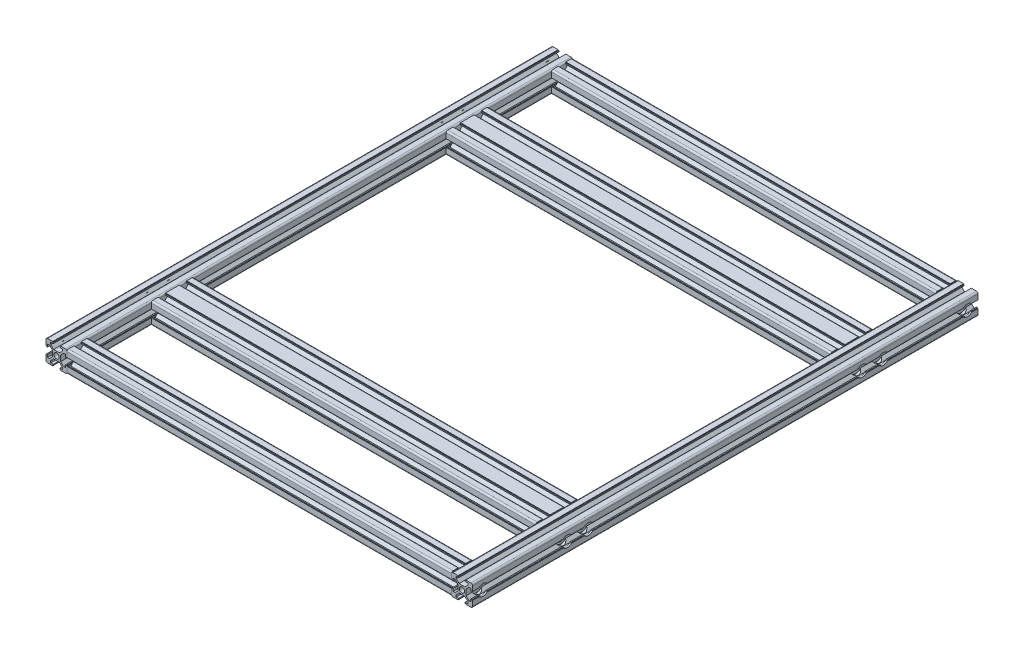
SolidWorks part; units mm, degrees
ref_plane "前视基准面" through (0, 0, 0) normal (0, 0, 1) x (1, 0, 0)
ref_plane "上视基准面" through (0, 0, 0) normal (0, 1, 0) x (1, 0, 0)
ref_plane "右视基准面" through (0, 0, 0) normal (1, 0, 0) x (0, 0, -1)
other "Configuration Table"
sketch "草图1" plane through (0, 0, 0) normal (0, 1, 0) x (1, 0, 0)
  line L0 (-192.5, 150) -> (-192.5, 230)
  line L1 (-192.5, 150) -> (192.5, 150)
  line L2 (-192.5, 150) -> (-192.5, -150)
  line L3 (-192.5, -150) -> (192.5, -150)
  line L4 (192.5, 150) -> (192.5, -150)
  line L5 (-192.5, 150) -> (192.5, -150) construction
  line L6 (-192.5, -150) -> (192.5, 150) construction
  line L7 (-192.5, 230) -> (192.5, 230)
  line L8 (192.5, 230) -> (192.5, 150)
  line L9 (-192.5, -150) -> (-192.5, -230)
  line L10 (-192.5, -230) -> (192.5, -230)
  line L11 (192.5, -230) -> (192.5, -150)
  point P0 (0, 0)
  dimension "D1" = 385
  dimension "D2" = 300
  dimension "D3" = 80
  dimension "D4" = 80
ref_plane "基准面1" through (-192.5, 0, -150) normal (0, 0, 1) x (1, 0, 0)
ref_plane "基准面2" through (-192.5, 0, 150) normal (1, 0, 0) x (0, 0, -1)
other "铝型材 20 X 20 X R1.5(1)"
ref_plane "基准面3" through (-192.5, 0, -230) normal (1, 0, 0) x (0, 0, -1)
sketch "Sketch1" plane through (-192.5, 0, -230) normal (1, 0, 0) x (0, 0, -1)
  line L0 (-3.6, 10) -> (-3.6, 9.5)
  line L1 (-3.6, 9.5) -> (-3.1, 9.5)
  line L2 (-3.1, 9.5) -> (-3.1, 8.5)
  line L3 (-3.1, 8.5) -> (-5.5, 8.5)
  line L4 (-8.5, -10) -> (-3.6, -10)
  line L5 (-10, -8.5) -> (-10, -3.6)
  line L6 (8.5, 10) -> (3.6, 10)
  line L7 (10, 8.5) -> (10, 3.6)
  line L8 (0, 14.8756) -> (0, 0) construction
  line L9 (0, 0) -> (14.1675, 0) construction
  line L10 (-5.5, 8.5) -> (-5.5, 6.65)
  line L11 (-5.5, 6.65) -> (-2.75, 3.9)
  line L12 (-2.75, 3.9) -> (2.75, 3.9)
  line L13 (5.5, 6.65) -> (2.75, 3.9)
  line L14 (5.5, 8.5) -> (5.5, 6.65)
  line L15 (3.1, 8.5) -> (5.5, 8.5)
  line L16 (3.1, 9.5) -> (3.1, 8.5)
  line L17 (3.6, 9.5) -> (3.1, 9.5)
  line L18 (3.6, 10) -> (3.6, 9.5)
  line L19 (-3.6, 10) -> (-8.5, 10)
  line L20 (10, 3.6) -> (9.5, 3.6)
  line L21 (9.5, 3.6) -> (9.5, 3.1)
  line L22 (9.5, 3.1) -> (8.5, 3.1)
  line L23 (8.5, 3.1) -> (8.5, 5.5)
  line L24 (8.5, 5.5) -> (6.65, 5.5)
  line L25 (6.65, 5.5) -> (3.9, 2.75)
  line L26 (3.9, 2.75) -> (3.9, -2.75)
  line L27 (6.65, -5.5) -> (3.9, -2.75)
  line L28 (8.5, -5.5) -> (6.65, -5.5)
  line L29 (8.5, -3.1) -> (8.5, -5.5)
  line L30 (9.5, -3.1) -> (8.5, -3.1)
  line L31 (9.5, -3.6) -> (9.5, -3.1)
  line L32 (10, -3.6) -> (9.5, -3.6)
  line L33 (3.6, -10) -> (3.6, -9.5)
  line L34 (3.6, -9.5) -> (3.1, -9.5)
  line L35 (3.1, -9.5) -> (3.1, -8.5)
  line L36 (3.1, -8.5) -> (5.5, -8.5)
  line L37 (5.5, -8.5) -> (5.5, -6.65)
  line L38 (5.5, -6.65) -> (2.75, -3.9)
  line L39 (2.75, -3.9) -> (-2.75, -3.9)
  line L40 (-5.5, -6.65) -> (-2.75, -3.9)
  line L41 (-5.5, -8.5) -> (-5.5, -6.65)
  line L42 (-3.1, -8.5) -> (-5.5, -8.5)
  line L43 (-3.1, -9.5) -> (-3.1, -8.5)
  line L44 (-3.6, -9.5) -> (-3.1, -9.5)
  line L45 (-3.6, -10) -> (-3.6, -9.5)
  line L46 (-10, -3.6) -> (-9.5, -3.6)
  line L47 (-9.5, -3.6) -> (-9.5, -3.1)
  line L48 (-9.5, -3.1) -> (-8.5, -3.1)
  line L49 (-8.5, -3.1) -> (-8.5, -5.5)
  line L50 (-8.5, -5.5) -> (-6.65, -5.5)
  line L51 (-6.65, -5.5) -> (-3.9, -2.75)
  line L52 (-3.9, -2.75) -> (-3.9, 2.75)
  line L53 (-6.65, 5.5) -> (-3.9, 2.75)
  line L54 (-8.5, 5.5) -> (-6.65, 5.5)
  line L55 (-8.5, 3.1) -> (-8.5, 5.5)
  line L56 (-9.5, 3.1) -> (-8.5, 3.1)
  line L57 (-9.5, 3.6) -> (-9.5, 3.1)
  line L58 (-10, 3.6) -> (-9.5, 3.6)
  line L59 (3.6, -10) -> (8.5, -10)
  line L60 (-10, 3.6) -> (-10, 8.5)
  line L61 (10, -3.6) -> (10, -8.5)
  circle A0 centre (0, 0) radius 2.5
  arc A1 (-10, 8.5) -> (-8.5, 10) centre (-8.5, 8.5) cw
  arc A2 (10, 8.5) -> (8.5, 10) centre (8.5, 8.5) ccw
  arc A3 (-8.5, -10) -> (-10, -8.5) centre (-8.5, -8.5) cw
  arc A4 (8.5, -10) -> (10, -8.5) centre (8.5, -8.5) ccw
  point P0 (-10, 0)
  point P1 (10, 0)
  point P2 (0, 10)
  point P3 (0, -10)
  point P4 (0, 0)
  point P5 (-10, -10)
  point P6 (10, -10)
  point P7 (10, 10)
  point P8 (-10, 10)
  point P13 (0, 0)
  point P36 (-10, 10)
  point P39 (10, 10)
  dimension "D1" = 11
  dimension "D2" = 20
  dimension "D3" = 6.2
  dimension "D4" = 7.2
  dimension "D5" = 6.1
  dimension "D6" = 5
  dimension "D7" = 1.5
  dimension "D8" = 45
  dimension "D9" = 0.5
  dimension "D10" = 1
  dimension "D11" = 5.5
other "铝型材 20 X 40 X R1.5(3)"
ref_plane "基准面8" through (-192.5, 0, 150) normal (1, 0, 0) x (0, 1, 0)
sketch "Sketch110" plane through (-192.5, 0, 150) normal (1, 0, 0) x (0, 1, 0)
  line L0 (-3.6, 10) -> (-3.6, 9.5)
  line L1 (-3.6, 9.5) -> (-3.1, 9.5)
  line L2 (-3.1, 9.5) -> (-3.1, 8.5)
  line L3 (-3.1, 8.5) -> (-5.5, 8.5)
  line L4 (8.85, -10) -> (2.75, -3.9)
  line L5 (-10, -16.4) -> (-10, -3.6)
  line L6 (8.5, 10) -> (3.6, 10)
  line L7 (10, 8.5) -> (10, 3.6)
  line L8 (0, 14.8756) -> (0, 0) construction
  line L9 (0, 0) -> (10, 0) construction
  line L10 (-5.5, 8.5) -> (-5.5, 6.65)
  line L11 (-5.5, 6.65) -> (-2.75, 3.9)
  line L12 (-2.75, 3.9) -> (2.75, 3.9)
  line L13 (5.5, 6.65) -> (2.75, 3.9)
  line L14 (5.5, 8.5) -> (5.5, 6.65)
  line L15 (3.1, 8.5) -> (5.5, 8.5)
  line L16 (3.1, 9.5) -> (3.1, 8.5)
  line L17 (3.6, 9.5) -> (3.1, 9.5)
  line L18 (3.6, 10) -> (3.6, 9.5)
  line L19 (-3.6, 10) -> (-8.5, 10)
  line L20 (10, 3.6) -> (9.5, 3.6)
  line L21 (9.5, 3.6) -> (9.5, 3.1)
  line L22 (9.5, 3.1) -> (8.5, 3.1)
  line L23 (8.5, 3.1) -> (8.5, 5.5)
  line L24 (8.5, 5.5) -> (6.65, 5.5)
  line L25 (6.65, 5.5) -> (3.9, 2.75)
  line L26 (3.9, 2.75) -> (3.9, -2.75)
  line L27 (6.65, -5.5) -> (3.9, -2.75)
  line L28 (8.5, -5.5) -> (6.65, -5.5)
  line L29 (8.5, -3.1) -> (8.5, -5.5)
  line L30 (9.5, -3.1) -> (8.5, -3.1)
  line L31 (9.5, -3.6) -> (9.5, -3.1)
  line L32 (10, -3.6) -> (9.5, -3.6)
  line L33 (8.85, -10) -> (2.75, -16.1)
  line L34 (-8.85, -10) -> (-2.75, -16.1)
  line L35 (-8.85, -10) -> (-2.75, -3.9)
  line L39 (2.75, -3.9) -> (-2.75, -3.9)
  line L46 (-10, -3.6) -> (-9.5, -3.6)
  line L47 (-9.5, -3.6) -> (-9.5, -3.1)
  line L48 (-9.5, -3.1) -> (-8.5, -3.1)
  line L49 (-8.5, -3.1) -> (-8.5, -5.5)
  line L50 (-8.5, -5.5) -> (-6.65, -5.5)
  line L51 (-6.65, -5.5) -> (-3.9, -2.75)
  line L52 (-3.9, -2.75) -> (-3.9, 2.75)
  line L53 (-6.65, 5.5) -> (-3.9, 2.75)
  line L54 (-8.5, 5.5) -> (-6.65, 5.5)
  line L55 (-8.5, 3.1) -> (-8.5, 5.5)
  line L56 (-9.5, 3.1) -> (-8.5, 3.1)
  line L57 (-9.5, 3.6) -> (-9.5, 3.1)
  line L58 (-10, 3.6) -> (-9.5, 3.6)
  line L60 (-10, 3.6) -> (-10, 8.5)
  line L61 (10, -3.6) -> (10, -16.4)
  line L66 (-8.5, -30) -> (-3.6, -30)
  line L67 (-10, -28.5) -> (-10, -23.6)
  line L72 (-2.75, -16.1) -> (2.75, -16.1)
  line L80 (10, -16.4) -> (9.5, -16.4)
  line L81 (9.5, -16.4) -> (9.5, -16.9)
  line L82 (9.5, -16.9) -> (8.5, -16.9)
  line L83 (8.5, -16.9) -> (8.5, -14.5)
  line L84 (8.5, -14.5) -> (6.65, -14.5)
  line L85 (6.65, -14.5) -> (3.9, -17.25)
  line L86 (3.9, -17.25) -> (3.9, -22.75)
  line L87 (6.65, -25.5) -> (3.9, -22.75)
  line L88 (8.5, -25.5) -> (6.65, -25.5)
  line L89 (8.5, -23.1) -> (8.5, -25.5)
  line L90 (9.5, -23.1) -> (8.5, -23.1)
  line L91 (9.5, -23.6) -> (9.5, -23.1)
  line L92 (10, -23.6) -> (9.5, -23.6)
  line L93 (3.6, -30) -> (3.6, -29.5)
  line L94 (3.6, -29.5) -> (3.1, -29.5)
  line L95 (3.1, -29.5) -> (3.1, -28.5)
  line L96 (3.1, -28.5) -> (5.5, -28.5)
  line L97 (5.5, -28.5) -> (5.5, -26.65)
  line L98 (5.5, -26.65) -> (2.75, -23.9)
  line L99 (2.75, -23.9) -> (-2.75, -23.9)
  line L100 (-5.5, -26.65) -> (-2.75, -23.9)
  line L101 (-5.5, -28.5) -> (-5.5, -26.65)
  line L102 (-3.1, -28.5) -> (-5.5, -28.5)
  line L103 (-3.1, -29.5) -> (-3.1, -28.5)
  line L104 (-3.6, -29.5) -> (-3.1, -29.5)
  line L105 (-3.6, -30) -> (-3.6, -29.5)
  line L106 (-10, -23.6) -> (-9.5, -23.6)
  line L107 (-9.5, -23.6) -> (-9.5, -23.1)
  line L108 (-9.5, -23.1) -> (-8.5, -23.1)
  line L109 (-8.5, -23.1) -> (-8.5, -25.5)
  line L110 (-8.5, -25.5) -> (-6.65, -25.5)
  line L111 (-6.65, -25.5) -> (-3.9, -22.75)
  line L112 (-3.9, -22.75) -> (-3.9, -17.25)
  line L113 (-6.65, -14.5) -> (-3.9, -17.25)
  line L114 (-8.5, -14.5) -> (-6.65, -14.5)
  line L115 (-8.5, -16.9) -> (-8.5, -14.5)
  line L116 (-9.5, -16.9) -> (-8.5, -16.9)
  line L117 (-9.5, -16.4) -> (-9.5, -16.9)
  line L118 (-10, -16.4) -> (-9.5, -16.4)
  line L119 (3.6, -30) -> (8.5, -30)
  line L121 (10, -23.6) -> (10, -28.5)
  line L122 (0, -20) -> (10, -20) construction
  line L125 (3.6, -10) -> (3.6, -9.5)
  line L127 (3.6, -9.5) -> (3.1, -9.5)
  line L129 (3.1, -9.5) -> (3.1, -8.5)
  line L131 (3.1, -8.5) -> (5.5, -8.5)
  line L133 (-3.1, -8.5) -> (-5.5, -8.5)
  line L135 (-3.1, -9.5) -> (-3.1, -8.5)
  line L137 (-3.6, -9.5) -> (-3.1, -9.5)
  line L139 (-3.6, -10) -> (-3.6, -9.5)
  line L141 (-3.6, -10) -> (-3.6, -10.5)
  line L142 (-3.6, -10.5) -> (-3.1, -10.5)
  line L143 (-3.1, -10.5) -> (-3.1, -11.5)
  line L144 (-3.1, -11.5) -> (-5.5, -11.5)
  line L145 (8.5, -10) -> (3.6, -10)
  line L146 (3.1, -11.5) -> (5.5, -11.5)
  line L147 (3.1, -10.5) -> (3.1, -11.5)
  line L148 (3.6, -10.5) -> (3.1, -10.5)
  line L149 (3.6, -10) -> (3.6, -10.5)
  line L150 (-3.6, -10) -> (-8.5, -10)
  line L151 (-10, -16.4) -> (-10, -11.5)
  line L152 (10, -11.5) -> (10, -16.4)
  line L154 (-5.5, -8.5) -> (-5.5, -6.65)
  line L156 (5.5, -8.5) -> (5.5, -6.65)
  line L157 (5.5, -11.5) -> (5.5, -13.35)
  line L158 (-5.5, -11.5) -> (-5.5, -13.35)
  line L160 (-12.2446, -13.3946) -> (-10, -11.15)
  line L161 (13.644, -5.206) -> (10, -8.85)
  line L163 (12.1963, -13.3463) -> (10, -11.15)
  line L164 (-11.1344, -7.7156) -> (-10, -8.85)
  circle A0 centre (0, 0) radius 2.5
  arc A1 (-10, 8.5) -> (-8.5, 10) centre (-8.5, 8.5) cw
  arc A2 (10, 8.5) -> (8.5, 10) centre (8.5, 8.5) ccw
  arc A3 (10, -28.5) -> (8.5, -30) centre (8.5, -28.5) cw
  arc A4 (-10, -28.5) -> (-8.5, -30) centre (-8.5, -28.5) ccw
  circle A5 centre (0, -20) radius 2.5
  arc A12 (-10, -11.5) -> (-8.5, -10) centre (-8.5, -11.5) cw
  arc A13 (10, -11.5) -> (8.5, -10) centre (8.5, -11.5) ccw
  point P0 (-10, 0)
  point P1 (10, 0)
  point P2 (0, 10)
  point P4 (0, 0)
  point P5 (0, -10)
  point P6 (-10, -10)
  point P7 (10, 10)
  point P8 (-10, 10)
  point P12 (-10, -10)
  point P13 (10, -10)
  point P15 (0, -10)
  point P16 (10, -10)
  point P36 (-10, 10)
  point P39 (10, 10)
  point P43 (-10, -20)
  point P44 (10, -20)
  point P62 (0, 0)
  point P88 (0, -30)
  point P89 (0, -20)
  point P90 (-10, -30)
  point P91 (10, -30)
  dimension "D1" = 11
  dimension "D2" = 20
  dimension "D3" = 6.2
  dimension "D4" = 7.2
  dimension "D5" = 6.1
  dimension "D6" = 5
  dimension "D7" = 1.5
  dimension "D8" = 45
  dimension "D14" = 20
  dimension "D15" = 1.5
  dimension "D9" = 0.5
  dimension "D10" = 1
  dimension "D11" = 5.5
  dimension "D12" = 10
  dimension "D13" = 40
  dimension "D16" = 45
  dimension "D17" = 45
  dimension "D18" = 45
  dimension "D19" = 6.2
other "铝型材 20 X 40 X R1.5(4)"
ref_plane "基准面9" through (-192.5, 0, -150) normal (1, 0, 0) x (0, -1, 0)
sketch "Sketch111" plane through (-192.5, 0, -150) normal (1, 0, 0) x (0, -1, 0)
  line L0 (-3.6, 10) -> (-3.6, 9.5)
  line L1 (-3.6, 9.5) -> (-3.1, 9.5)
  line L2 (-3.1, 9.5) -> (-3.1, 8.5)
  line L3 (-3.1, 8.5) -> (-5.5, 8.5)
  line L4 (8.85, -10) -> (2.75, -3.9)
  line L5 (-10, -16.4) -> (-10, -3.6)
  line L6 (8.5, 10) -> (3.6, 10)
  line L7 (10, 8.5) -> (10, 3.6)
  line L8 (0, 14.8756) -> (0, 0) construction
  line L9 (0, 0) -> (10, 0) construction
  line L10 (-5.5, 8.5) -> (-5.5, 6.65)
  line L11 (-5.5, 6.65) -> (-2.75, 3.9)
  line L12 (-2.75, 3.9) -> (2.75, 3.9)
  line L13 (5.5, 6.65) -> (2.75, 3.9)
  line L14 (5.5, 8.5) -> (5.5, 6.65)
  line L15 (3.1, 8.5) -> (5.5, 8.5)
  line L16 (3.1, 9.5) -> (3.1, 8.5)
  line L17 (3.6, 9.5) -> (3.1, 9.5)
  line L18 (3.6, 10) -> (3.6, 9.5)
  line L19 (-3.6, 10) -> (-8.5, 10)
  line L20 (10, 3.6) -> (9.5, 3.6)
  line L21 (9.5, 3.6) -> (9.5, 3.1)
  line L22 (9.5, 3.1) -> (8.5, 3.1)
  line L23 (8.5, 3.1) -> (8.5, 5.5)
  line L24 (8.5, 5.5) -> (6.65, 5.5)
  line L25 (6.65, 5.5) -> (3.9, 2.75)
  line L26 (3.9, 2.75) -> (3.9, -2.75)
  line L27 (6.65, -5.5) -> (3.9, -2.75)
  line L28 (8.5, -5.5) -> (6.65, -5.5)
  line L29 (8.5, -3.1) -> (8.5, -5.5)
  line L30 (9.5, -3.1) -> (8.5, -3.1)
  line L31 (9.5, -3.6) -> (9.5, -3.1)
  line L32 (10, -3.6) -> (9.5, -3.6)
  line L33 (8.85, -10) -> (2.75, -16.1)
  line L34 (-8.85, -10) -> (-2.75, -16.1)
  line L35 (-8.85, -10) -> (-2.75, -3.9)
  line L39 (2.75, -3.9) -> (-2.75, -3.9)
  line L46 (-10, -3.6) -> (-9.5, -3.6)
  line L47 (-9.5, -3.6) -> (-9.5, -3.1)
  line L48 (-9.5, -3.1) -> (-8.5, -3.1)
  line L49 (-8.5, -3.1) -> (-8.5, -5.5)
  line L50 (-8.5, -5.5) -> (-6.65, -5.5)
  line L51 (-6.65, -5.5) -> (-3.9, -2.75)
  line L52 (-3.9, -2.75) -> (-3.9, 2.75)
  line L53 (-6.65, 5.5) -> (-3.9, 2.75)
  line L54 (-8.5, 5.5) -> (-6.65, 5.5)
  line L55 (-8.5, 3.1) -> (-8.5, 5.5)
  line L56 (-9.5, 3.1) -> (-8.5, 3.1)
  line L57 (-9.5, 3.6) -> (-9.5, 3.1)
  line L58 (-10, 3.6) -> (-9.5, 3.6)
  line L60 (-10, 3.6) -> (-10, 8.5)
  line L61 (10, -3.6) -> (10, -16.4)
  line L66 (-8.5, -30) -> (-3.6, -30)
  line L67 (-10, -28.5) -> (-10, -23.6)
  line L72 (-2.75, -16.1) -> (2.75, -16.1)
  line L80 (10, -16.4) -> (9.5, -16.4)
  line L81 (9.5, -16.4) -> (9.5, -16.9)
  line L82 (9.5, -16.9) -> (8.5, -16.9)
  line L83 (8.5, -16.9) -> (8.5, -14.5)
  line L84 (8.5, -14.5) -> (6.65, -14.5)
  line L85 (6.65, -14.5) -> (3.9, -17.25)
  line L86 (3.9, -17.25) -> (3.9, -22.75)
  line L87 (6.65, -25.5) -> (3.9, -22.75)
  line L88 (8.5, -25.5) -> (6.65, -25.5)
  line L89 (8.5, -23.1) -> (8.5, -25.5)
  line L90 (9.5, -23.1) -> (8.5, -23.1)
  line L91 (9.5, -23.6) -> (9.5, -23.1)
  line L92 (10, -23.6) -> (9.5, -23.6)
  line L93 (3.6, -30) -> (3.6, -29.5)
  line L94 (3.6, -29.5) -> (3.1, -29.5)
  line L95 (3.1, -29.5) -> (3.1, -28.5)
  line L96 (3.1, -28.5) -> (5.5, -28.5)
  line L97 (5.5, -28.5) -> (5.5, -26.65)
  line L98 (5.5, -26.65) -> (2.75, -23.9)
  line L99 (2.75, -23.9) -> (-2.75, -23.9)
  line L100 (-5.5, -26.65) -> (-2.75, -23.9)
  line L101 (-5.5, -28.5) -> (-5.5, -26.65)
  line L102 (-3.1, -28.5) -> (-5.5, -28.5)
  line L103 (-3.1, -29.5) -> (-3.1, -28.5)
  line L104 (-3.6, -29.5) -> (-3.1, -29.5)
  line L105 (-3.6, -30) -> (-3.6, -29.5)
  line L106 (-10, -23.6) -> (-9.5, -23.6)
  line L107 (-9.5, -23.6) -> (-9.5, -23.1)
  line L108 (-9.5, -23.1) -> (-8.5, -23.1)
  line L109 (-8.5, -23.1) -> (-8.5, -25.5)
  line L110 (-8.5, -25.5) -> (-6.65, -25.5)
  line L111 (-6.65, -25.5) -> (-3.9, -22.75)
  line L112 (-3.9, -22.75) -> (-3.9, -17.25)
  line L113 (-6.65, -14.5) -> (-3.9, -17.25)
  line L114 (-8.5, -14.5) -> (-6.65, -14.5)
  line L115 (-8.5, -16.9) -> (-8.5, -14.5)
  line L116 (-9.5, -16.9) -> (-8.5, -16.9)
  line L117 (-9.5, -16.4) -> (-9.5, -16.9)
  line L118 (-10, -16.4) -> (-9.5, -16.4)
  line L119 (3.6, -30) -> (8.5, -30)
  line L121 (10, -23.6) -> (10, -28.5)
  line L122 (0, -20) -> (10, -20) construction
  line L125 (3.6, -10) -> (3.6, -9.5)
  line L127 (3.6, -9.5) -> (3.1, -9.5)
  line L129 (3.1, -9.5) -> (3.1, -8.5)
  line L131 (3.1, -8.5) -> (5.5, -8.5)
  line L133 (-3.1, -8.5) -> (-5.5, -8.5)
  line L135 (-3.1, -9.5) -> (-3.1, -8.5)
  line L137 (-3.6, -9.5) -> (-3.1, -9.5)
  line L139 (-3.6, -10) -> (-3.6, -9.5)
  line L141 (-3.6, -10) -> (-3.6, -10.5)
  line L142 (-3.6, -10.5) -> (-3.1, -10.5)
  line L143 (-3.1, -10.5) -> (-3.1, -11.5)
  line L144 (-3.1, -11.5) -> (-5.5, -11.5)
  line L145 (8.5, -10) -> (3.6, -10)
  line L146 (3.1, -11.5) -> (5.5, -11.5)
  line L147 (3.1, -10.5) -> (3.1, -11.5)
  line L148 (3.6, -10.5) -> (3.1, -10.5)
  line L149 (3.6, -10) -> (3.6, -10.5)
  line L150 (-3.6, -10) -> (-8.5, -10)
  line L151 (-10, -16.4) -> (-10, -11.5)
  line L152 (10, -11.5) -> (10, -16.4)
  line L154 (-5.5, -8.5) -> (-5.5, -6.65)
  line L156 (5.5, -8.5) -> (5.5, -6.65)
  line L157 (5.5, -11.5) -> (5.5, -13.35)
  line L158 (-5.5, -11.5) -> (-5.5, -13.35)
  line L160 (-12.2446, -13.3946) -> (-10, -11.15)
  line L161 (13.644, -5.206) -> (10, -8.85)
  line L163 (12.1963, -13.3463) -> (10, -11.15)
  line L164 (-11.1344, -7.7156) -> (-10, -8.85)
  circle A0 centre (0, 0) radius 2.5
  arc A1 (-10, 8.5) -> (-8.5, 10) centre (-8.5, 8.5) cw
  arc A2 (10, 8.5) -> (8.5, 10) centre (8.5, 8.5) ccw
  arc A3 (10, -28.5) -> (8.5, -30) centre (8.5, -28.5) cw
  arc A4 (-10, -28.5) -> (-8.5, -30) centre (-8.5, -28.5) ccw
  circle A5 centre (0, -20) radius 2.5
  arc A12 (-10, -11.5) -> (-8.5, -10) centre (-8.5, -11.5) cw
  arc A13 (10, -11.5) -> (8.5, -10) centre (8.5, -11.5) ccw
  point P0 (-10, 0)
  point P1 (10, 0)
  point P2 (0, 10)
  point P4 (0, 0)
  point P5 (0, -10)
  point P6 (-10, -10)
  point P7 (10, 10)
  point P8 (-10, 10)
  point P12 (-10, -10)
  point P13 (10, -10)
  point P15 (0, -10)
  point P16 (10, -10)
  point P36 (-10, 10)
  point P39 (10, 10)
  point P43 (-10, -20)
  point P44 (10, -20)
  point P62 (0, 0)
  point P88 (0, -30)
  point P89 (0, -20)
  point P90 (-10, -30)
  point P91 (10, -30)
  dimension "D1" = 11
  dimension "D2" = 20
  dimension "D3" = 6.2
  dimension "D4" = 7.2
  dimension "D5" = 6.1
  dimension "D6" = 5
  dimension "D7" = 1.5
  dimension "D8" = 45
  dimension "D14" = 20
  dimension "D15" = 1.5
  dimension "D9" = 0.5
  dimension "D10" = 1
  dimension "D11" = 5.5
  dimension "D12" = 10
  dimension "D13" = 40
  dimension "D16" = 45
  dimension "D17" = 45
  dimension "D18" = 45
  dimension "D19" = 6.2
other "铝型材 20 X 20 X R1.5(24)"
ref_plane "基准面10" through (-192.5, 0, 150) normal (0, 0, 1) x (1, 0, 0)
sketch "Sketch114" plane through (-192.5, 0, 150) normal (0, 0, 1) x (1, 0, 0)
  line L0 (-3.6, 10) -> (-3.6, 9.5)
  line L1 (-3.6, 9.5) -> (-3.1, 9.5)
  line L2 (-3.1, 9.5) -> (-3.1, 8.5)
  line L3 (-3.1, 8.5) -> (-5.5, 8.5)
  line L4 (-8.5, -10) -> (-3.6, -10)
  line L5 (-10, -8.5) -> (-10, -3.6)
  line L6 (8.5, 10) -> (3.6, 10)
  line L7 (10, 8.5) -> (10, 3.6)
  line L8 (0, 14.8756) -> (0, 0) construction
  line L9 (0, 0) -> (14.1675, 0) construction
  line L10 (-5.5, 8.5) -> (-5.5, 6.65)
  line L11 (-5.5, 6.65) -> (-2.75, 3.9)
  line L12 (-2.75, 3.9) -> (2.75, 3.9)
  line L13 (5.5, 6.65) -> (2.75, 3.9)
  line L14 (5.5, 8.5) -> (5.5, 6.65)
  line L15 (3.1, 8.5) -> (5.5, 8.5)
  line L16 (3.1, 9.5) -> (3.1, 8.5)
  line L17 (3.6, 9.5) -> (3.1, 9.5)
  line L18 (3.6, 10) -> (3.6, 9.5)
  line L19 (-3.6, 10) -> (-8.5, 10)
  line L20 (10, 3.6) -> (9.5, 3.6)
  line L21 (9.5, 3.6) -> (9.5, 3.1)
  line L22 (9.5, 3.1) -> (8.5, 3.1)
  line L23 (8.5, 3.1) -> (8.5, 5.5)
  line L24 (8.5, 5.5) -> (6.65, 5.5)
  line L25 (6.65, 5.5) -> (3.9, 2.75)
  line L26 (3.9, 2.75) -> (3.9, -2.75)
  line L27 (6.65, -5.5) -> (3.9, -2.75)
  line L28 (8.5, -5.5) -> (6.65, -5.5)
  line L29 (8.5, -3.1) -> (8.5, -5.5)
  line L30 (9.5, -3.1) -> (8.5, -3.1)
  line L31 (9.5, -3.6) -> (9.5, -3.1)
  line L32 (10, -3.6) -> (9.5, -3.6)
  line L33 (3.6, -10) -> (3.6, -9.5)
  line L34 (3.6, -9.5) -> (3.1, -9.5)
  line L35 (3.1, -9.5) -> (3.1, -8.5)
  line L36 (3.1, -8.5) -> (5.5, -8.5)
  line L37 (5.5, -8.5) -> (5.5, -6.65)
  line L38 (5.5, -6.65) -> (2.75, -3.9)
  line L39 (2.75, -3.9) -> (-2.75, -3.9)
  line L40 (-5.5, -6.65) -> (-2.75, -3.9)
  line L41 (-5.5, -8.5) -> (-5.5, -6.65)
  line L42 (-3.1, -8.5) -> (-5.5, -8.5)
  line L43 (-3.1, -9.5) -> (-3.1, -8.5)
  line L44 (-3.6, -9.5) -> (-3.1, -9.5)
  line L45 (-3.6, -10) -> (-3.6, -9.5)
  line L46 (-10, -3.6) -> (-9.5, -3.6)
  line L47 (-9.5, -3.6) -> (-9.5, -3.1)
  line L48 (-9.5, -3.1) -> (-8.5, -3.1)
  line L49 (-8.5, -3.1) -> (-8.5, -5.5)
  line L50 (-8.5, -5.5) -> (-6.65, -5.5)
  line L51 (-6.65, -5.5) -> (-3.9, -2.75)
  line L52 (-3.9, -2.75) -> (-3.9, 2.75)
  line L53 (-6.65, 5.5) -> (-3.9, 2.75)
  line L54 (-8.5, 5.5) -> (-6.65, 5.5)
  line L55 (-8.5, 3.1) -> (-8.5, 5.5)
  line L56 (-9.5, 3.1) -> (-8.5, 3.1)
  line L57 (-9.5, 3.6) -> (-9.5, 3.1)
  line L58 (-10, 3.6) -> (-9.5, 3.6)
  line L59 (3.6, -10) -> (8.5, -10)
  line L60 (-10, 3.6) -> (-10, 8.5)
  line L61 (10, -3.6) -> (10, -8.5)
  circle A0 centre (0, 0) radius 2.5
  arc A1 (-10, 8.5) -> (-8.5, 10) centre (-8.5, 8.5) cw
  arc A2 (10, 8.5) -> (8.5, 10) centre (8.5, 8.5) ccw
  arc A3 (-8.5, -10) -> (-10, -8.5) centre (-8.5, -8.5) cw
  arc A4 (8.5, -10) -> (10, -8.5) centre (8.5, -8.5) ccw
  point P0 (-10, 0)
  point P1 (10, 0)
  point P2 (0, 10)
  point P3 (0, -10)
  point P4 (0, 0)
  point P5 (-10, -10)
  point P6 (10, -10)
  point P7 (10, 10)
  point P8 (-10, 10)
  point P13 (0, 0)
  point P36 (-10, 10)
  point P39 (10, 10)
  dimension "D1" = 11
  dimension "D2" = 20
  dimension "D3" = 6.2
  dimension "D4" = 7.2
  dimension "D5" = 6.1
  dimension "D6" = 5
  dimension "D7" = 1.5
  dimension "D8" = 45
  dimension "D9" = 0.5
  dimension "D10" = 1
  dimension "D11" = 5.5
other "铝型材 20 X 20 X R1.5(25)"
ref_plane "基准面11" through (192.5, 0, 230) normal (0, 0, -1) x (-1, 0, 0)
sketch "Sketch115" plane through (192.5, 0, 230) normal (0, 0, -1) x (-1, 0, 0)
  line L0 (-3.6, 10) -> (-3.6, 9.5)
  line L1 (-3.6, 9.5) -> (-3.1, 9.5)
  line L2 (-3.1, 9.5) -> (-3.1, 8.5)
  line L3 (-3.1, 8.5) -> (-5.5, 8.5)
  line L4 (-8.5, -10) -> (-3.6, -10)
  line L5 (-10, -8.5) -> (-10, -3.6)
  line L6 (8.5, 10) -> (3.6, 10)
  line L7 (10, 8.5) -> (10, 3.6)
  line L8 (0, 14.8756) -> (0, 0) construction
  line L9 (0, 0) -> (14.1675, 0) construction
  line L10 (-5.5, 8.5) -> (-5.5, 6.65)
  line L11 (-5.5, 6.65) -> (-2.75, 3.9)
  line L12 (-2.75, 3.9) -> (2.75, 3.9)
  line L13 (5.5, 6.65) -> (2.75, 3.9)
  line L14 (5.5, 8.5) -> (5.5, 6.65)
  line L15 (3.1, 8.5) -> (5.5, 8.5)
  line L16 (3.1, 9.5) -> (3.1, 8.5)
  line L17 (3.6, 9.5) -> (3.1, 9.5)
  line L18 (3.6, 10) -> (3.6, 9.5)
  line L19 (-3.6, 10) -> (-8.5, 10)
  line L20 (10, 3.6) -> (9.5, 3.6)
  line L21 (9.5, 3.6) -> (9.5, 3.1)
  line L22 (9.5, 3.1) -> (8.5, 3.1)
  line L23 (8.5, 3.1) -> (8.5, 5.5)
  line L24 (8.5, 5.5) -> (6.65, 5.5)
  line L25 (6.65, 5.5) -> (3.9, 2.75)
  line L26 (3.9, 2.75) -> (3.9, -2.75)
  line L27 (6.65, -5.5) -> (3.9, -2.75)
  line L28 (8.5, -5.5) -> (6.65, -5.5)
  line L29 (8.5, -3.1) -> (8.5, -5.5)
  line L30 (9.5, -3.1) -> (8.5, -3.1)
  line L31 (9.5, -3.6) -> (9.5, -3.1)
  line L32 (10, -3.6) -> (9.5, -3.6)
  line L33 (3.6, -10) -> (3.6, -9.5)
  line L34 (3.6, -9.5) -> (3.1, -9.5)
  line L35 (3.1, -9.5) -> (3.1, -8.5)
  line L36 (3.1, -8.5) -> (5.5, -8.5)
  line L37 (5.5, -8.5) -> (5.5, -6.65)
  line L38 (5.5, -6.65) -> (2.75, -3.9)
  line L39 (2.75, -3.9) -> (-2.75, -3.9)
  line L40 (-5.5, -6.65) -> (-2.75, -3.9)
  line L41 (-5.5, -8.5) -> (-5.5, -6.65)
  line L42 (-3.1, -8.5) -> (-5.5, -8.5)
  line L43 (-3.1, -9.5) -> (-3.1, -8.5)
  line L44 (-3.6, -9.5) -> (-3.1, -9.5)
  line L45 (-3.6, -10) -> (-3.6, -9.5)
  line L46 (-10, -3.6) -> (-9.5, -3.6)
  line L47 (-9.5, -3.6) -> (-9.5, -3.1)
  line L48 (-9.5, -3.1) -> (-8.5, -3.1)
  line L49 (-8.5, -3.1) -> (-8.5, -5.5)
  line L50 (-8.5, -5.5) -> (-6.65, -5.5)
  line L51 (-6.65, -5.5) -> (-3.9, -2.75)
  line L52 (-3.9, -2.75) -> (-3.9, 2.75)
  line L53 (-6.65, 5.5) -> (-3.9, 2.75)
  line L54 (-8.5, 5.5) -> (-6.65, 5.5)
  line L55 (-8.5, 3.1) -> (-8.5, 5.5)
  line L56 (-9.5, 3.1) -> (-8.5, 3.1)
  line L57 (-9.5, 3.6) -> (-9.5, 3.1)
  line L58 (-10, 3.6) -> (-9.5, 3.6)
  line L59 (3.6, -10) -> (8.5, -10)
  line L60 (-10, 3.6) -> (-10, 8.5)
  line L61 (10, -3.6) -> (10, -8.5)
  circle A0 centre (0, 0) radius 2.5
  arc A1 (-10, 8.5) -> (-8.5, 10) centre (-8.5, 8.5) cw
  arc A2 (10, 8.5) -> (8.5, 10) centre (8.5, 8.5) ccw
  arc A3 (-8.5, -10) -> (-10, -8.5) centre (-8.5, -8.5) cw
  arc A4 (8.5, -10) -> (10, -8.5) centre (8.5, -8.5) ccw
  point P0 (-10, 0)
  point P1 (10, 0)
  point P2 (0, 10)
  point P3 (0, -10)
  point P4 (0, 0)
  point P5 (-10, -10)
  point P6 (10, -10)
  point P7 (10, 10)
  point P8 (-10, 10)
  point P13 (0, 0)
  point P36 (-10, 10)
  point P39 (10, 10)
  dimension "D1" = 11
  dimension "D2" = 20
  dimension "D3" = 6.2
  dimension "D4" = 7.2
  dimension "D5" = 6.1
  dimension "D6" = 5
  dimension "D7" = 1.5
  dimension "D8" = 45
  dimension "D9" = 0.5
  dimension "D10" = 1
  dimension "D11" = 5.5
other "剪裁/延伸3"
other "剪裁/延伸4"
other "剪裁/延伸5"
other "剪裁/延伸6"
combine bodies "组合1" operation type add bodies to combine 142 133 140
combine bodies "组合2" operation type add bodies to combine 141 130 139
sketch "草图16" plane through (-202.5, 0, 0) normal (-1, 0, 0) x (0, 0, 1)
  line L0 (121.5, 8.5) -> (140, -10) construction
  line L1 (140, -10) -> (158.5, 8.5) construction
  line L2 (153.9, 0) -> (126.1, 0) construction
  line L9 (-140, -8.85) -> (-133.9, -2.75)
  line L10 (-146.1, -2.75) -> (-140, -8.85)
  line L11 (-146.1, 2.75) -> (-146.1, -2.75)
  line L12 (-140, 8.85) -> (-146.1, 2.75)
  line L13 (-133.9, 2.75) -> (-140, 8.85)
  line L14 (-133.9, -2.75) -> (-133.9, 2.75)
  line L15 (-140, -8.85) -> (-133.9, -2.75)
  line L16 (-146.1, -2.75) -> (-140, -8.85)
  line L17 (-146.1, 2.75) -> (-146.1, -2.75)
  line L18 (-140, 8.85) -> (-146.1, 2.75)
  line L19 (-133.9, 2.75) -> (-140, 8.85)
  line L20 (-133.9, -2.75) -> (-133.9, 2.75)
  line L88 (160, -3.6) -> (159.5, -3.6)
  line L89 (159.5, -3.6) -> (159.5, -3.1)
  line L90 (159.5, -3.1) -> (158.5, -3.1)
  line L91 (158.5, -3.1) -> (158.5, -5.5)
  line L92 (158.5, -5.5) -> (156.65, -5.5)
  line L93 (156.65, -5.5) -> (153.9, -2.75)
  line L94 (153.9, -2.75) -> (153.9, 2.75)
  line L95 (153.9, 2.75) -> (156.65, 5.5)
  line L96 (156.65, 5.5) -> (158.5, 5.5)
  line L97 (158.5, 5.5) -> (158.5, 3.1)
  line L98 (158.5, 3.1) -> (159.5, 3.1)
  line L99 (159.5, 3.1) -> (159.5, 3.6)
  line L100 (159.5, 3.6) -> (160, 3.6)
  line L101 (160, 3.6) -> (160, 8.5)
  line L102 (158.5, 10) -> (153.6, 10)
  line L103 (153.6, 10) -> (153.6, 9.5)
  line L104 (153.6, 9.5) -> (153.1, 9.5)
  line L105 (153.1, 9.5) -> (153.1, 8.5)
  line L106 (153.1, 8.5) -> (155.5, 8.5)
  line L107 (155.5, 8.5) -> (155.5, 6.65)
  line L108 (155.5, 6.65) -> (152.75, 3.9)
  line L109 (152.75, 3.9) -> (147.25, 3.9)
  line L110 (147.25, 3.9) -> (144.5, 6.65)
  line L111 (144.5, 6.65) -> (144.5, 8.5)
  line L112 (144.5, 8.5) -> (146.9, 8.5)
  line L113 (146.9, 8.5) -> (146.9, 9.5)
  line L114 (146.9, 9.5) -> (146.4, 9.5)
  line L115 (146.4, 9.5) -> (146.4, 10)
  line L116 (146.4, 10) -> (133.6, 10)
  line L117 (133.6, 10) -> (133.6, 9.5)
  line L118 (133.6, 9.5) -> (133.1, 9.5)
  line L119 (133.1, 9.5) -> (133.1, 8.5)
  line L120 (133.1, 8.5) -> (135.5, 8.5)
  line L121 (135.5, 8.5) -> (135.5, 6.65)
  line L122 (135.5, 6.65) -> (132.75, 3.9)
  line L123 (132.75, 3.9) -> (127.25, 3.9)
  line L124 (127.25, 3.9) -> (124.5, 6.65)
  line L125 (124.5, 6.65) -> (124.5, 8.5)
  line L126 (124.5, 8.5) -> (126.9, 8.5)
  line L127 (126.9, 8.5) -> (126.9, 9.5)
  line L128 (126.9, 9.5) -> (126.4, 9.5)
  line L129 (126.4, 9.5) -> (126.4, 10)
  line L130 (126.4, 10) -> (121.5, 10)
  line L131 (120, 8.5) -> (120, 3.6)
  line L132 (120, 3.6) -> (120.5, 3.6)
  line L133 (120.5, 3.6) -> (120.5, 3.1)
  line L134 (120.5, 3.1) -> (121.5, 3.1)
  line L135 (121.5, 3.1) -> (121.5, 5.5)
  line L136 (121.5, 5.5) -> (123.35, 5.5)
  line L137 (123.35, 5.5) -> (126.1, 2.75)
  line L138 (126.1, 2.75) -> (126.1, -2.75)
  line L139 (126.1, -2.75) -> (123.35, -5.5)
  line L140 (123.35, -5.5) -> (121.5, -5.5)
  line L141 (121.5, -5.5) -> (121.5, -3.1)
  line L142 (121.5, -3.1) -> (120.5, -3.1)
  line L143 (120.5, -3.1) -> (120.5, -3.6)
  line L144 (120.5, -3.6) -> (120, -3.6)
  line L145 (120, -3.6) -> (120, -8.5)
  line L146 (121.5, -10) -> (126.4, -10)
  line L147 (126.4, -10) -> (126.4, -9.5)
  line L148 (126.4, -9.5) -> (126.9, -9.5)
  line L149 (126.9, -9.5) -> (126.9, -8.5)
  line L150 (126.9, -8.5) -> (124.5, -8.5)
  line L151 (124.5, -8.5) -> (124.5, -6.65)
  line L152 (124.5, -6.65) -> (127.25, -3.9)
  line L153 (127.25, -3.9) -> (132.75, -3.9)
  line L154 (132.75, -3.9) -> (135.5, -6.65)
  line L155 (135.5, -6.65) -> (135.5, -8.5)
  line L156 (135.5, -8.5) -> (133.1, -8.5)
  line L157 (133.1, -8.5) -> (133.1, -9.5)
  line L158 (133.1, -9.5) -> (133.6, -9.5)
  line L159 (133.6, -9.5) -> (133.6, -10)
  line L160 (133.6, -10) -> (146.4, -10)
  line L161 (146.4, -10) -> (146.4, -9.5)
  line L162 (146.4, -9.5) -> (146.9, -9.5)
  line L163 (146.9, -9.5) -> (146.9, -8.5)
  line L164 (146.9, -8.5) -> (144.5, -8.5)
  line L165 (144.5, -8.5) -> (144.5, -6.65)
  line L166 (144.5, -6.65) -> (147.25, -3.9)
  line L167 (147.25, -3.9) -> (152.75, -3.9)
  line L168 (152.75, -3.9) -> (155.5, -6.65)
  line L169 (155.5, -6.65) -> (155.5, -8.5)
  line L170 (155.5, -8.5) -> (153.1, -8.5)
  line L171 (153.1, -8.5) -> (153.1, -9.5)
  line L172 (153.1, -9.5) -> (153.6, -9.5)
  line L173 (153.6, -9.5) -> (153.6, -10)
  line L174 (153.6, -10) -> (158.5, -10)
  line L175 (160, -8.5) -> (160, -3.6)
  line L176 (160, -3.6) -> (159.5, -3.6)
  line L177 (159.5, -3.6) -> (159.5, -3.1)
  line L178 (159.5, -3.1) -> (158.5, -3.1)
  line L179 (158.5, -3.1) -> (158.5, -5.5)
  line L180 (158.5, -5.5) -> (156.65, -5.5)
  line L181 (156.65, -5.5) -> (153.9, -2.75)
  line L182 (153.9, -2.75) -> (153.9, 2.75)
  line L183 (153.9, 2.75) -> (156.65, 5.5)
  line L184 (156.65, 5.5) -> (158.5, 5.5)
  line L185 (158.5, 5.5) -> (158.5, 3.1)
  line L186 (158.5, 3.1) -> (159.5, 3.1)
  line L187 (159.5, 3.1) -> (159.5, 3.6)
  line L188 (159.5, 3.6) -> (160, 3.6)
  line L189 (160, 3.6) -> (160, 8.5)
  line L190 (158.5, 10) -> (153.6, 10)
  line L191 (153.6, 10) -> (153.6, 9.5)
  line L192 (153.6, 9.5) -> (153.1, 9.5)
  line L193 (153.1, 9.5) -> (153.1, 8.5)
  line L194 (153.1, 8.5) -> (155.5, 8.5)
  line L195 (155.5, 8.5) -> (155.5, 6.65)
  line L196 (155.5, 6.65) -> (152.75, 3.9)
  line L197 (152.75, 3.9) -> (147.25, 3.9)
  line L198 (147.25, 3.9) -> (144.5, 6.65)
  line L199 (144.5, 6.65) -> (144.5, 8.5)
  line L200 (144.5, 8.5) -> (146.9, 8.5)
  line L201 (146.9, 8.5) -> (146.9, 9.5)
  line L202 (146.9, 9.5) -> (146.4, 9.5)
  line L203 (146.4, 9.5) -> (146.4, 10)
  line L204 (146.4, 10) -> (133.6, 10)
  line L205 (133.6, 10) -> (133.6, 9.5)
  line L206 (133.6, 9.5) -> (133.1, 9.5)
  line L207 (133.1, 9.5) -> (133.1, 8.5)
  line L208 (133.1, 8.5) -> (135.5, 8.5)
  line L209 (135.5, 8.5) -> (135.5, 6.65)
  line L210 (135.5, 6.65) -> (132.75, 3.9)
  line L211 (132.75, 3.9) -> (127.25, 3.9)
  line L212 (127.25, 3.9) -> (124.5, 6.65)
  line L213 (124.5, 6.65) -> (124.5, 8.5)
  line L214 (124.5, 8.5) -> (126.9, 8.5)
  line L215 (126.9, 8.5) -> (126.9, 9.5)
  line L216 (126.9, 9.5) -> (126.4, 9.5)
  line L217 (126.4, 9.5) -> (126.4, 10)
  line L218 (126.4, 10) -> (121.5, 10)
  line L219 (120, 8.5) -> (120, 3.6)
  line L220 (120, 3.6) -> (120.5, 3.6)
  line L221 (120.5, 3.6) -> (120.5, 3.1)
  line L222 (120.5, 3.1) -> (121.5, 3.1)
  line L223 (121.5, 3.1) -> (121.5, 5.5)
  line L224 (121.5, 5.5) -> (123.35, 5.5)
  line L225 (123.35, 5.5) -> (126.1, 2.75)
  line L226 (126.1, 2.75) -> (126.1, -2.75)
  line L227 (126.1, -2.75) -> (123.35, -5.5)
  line L228 (123.35, -5.5) -> (121.5, -5.5)
  line L229 (121.5, -5.5) -> (121.5, -3.1)
  line L230 (121.5, -3.1) -> (120.5, -3.1)
  line L231 (120.5, -3.1) -> (120.5, -3.6)
  line L232 (120.5, -3.6) -> (120, -3.6)
  line L233 (120, -3.6) -> (120, -8.5)
  line L234 (121.5, -10) -> (126.4, -10)
  line L235 (126.4, -10) -> (126.4, -9.5)
  line L236 (126.4, -9.5) -> (126.9, -9.5)
  line L237 (126.9, -9.5) -> (126.9, -8.5)
  line L238 (126.9, -8.5) -> (124.5, -8.5)
  line L239 (124.5, -8.5) -> (124.5, -6.65)
  line L240 (124.5, -6.65) -> (127.25, -3.9)
  line L241 (127.25, -3.9) -> (132.75, -3.9)
  line L242 (132.75, -3.9) -> (135.5, -6.65)
  line L243 (135.5, -6.65) -> (135.5, -8.5)
  line L244 (135.5, -8.5) -> (133.1, -8.5)
  line L245 (133.1, -8.5) -> (133.1, -9.5)
  line L246 (133.1, -9.5) -> (133.6, -9.5)
  line L247 (133.6, -9.5) -> (133.6, -10)
  line L248 (133.6, -10) -> (146.4, -10)
  line L249 (146.4, -10) -> (146.4, -9.5)
  line L250 (146.4, -9.5) -> (146.9, -9.5)
  line L251 (146.9, -9.5) -> (146.9, -8.5)
  line L252 (146.9, -8.5) -> (144.5, -8.5)
  line L253 (144.5, -8.5) -> (144.5, -6.65)
  line L254 (144.5, -6.65) -> (147.25, -3.9)
  line L255 (147.25, -3.9) -> (152.75, -3.9)
  line L256 (152.75, -3.9) -> (155.5, -6.65)
  line L257 (155.5, -6.65) -> (155.5, -8.5)
  line L258 (155.5, -8.5) -> (153.1, -8.5)
  line L259 (153.1, -8.5) -> (153.1, -9.5)
  line L260 (153.1, -9.5) -> (153.6, -9.5)
  line L261 (153.6, -9.5) -> (153.6, -10)
  line L262 (153.6, -10) -> (158.5, -10)
  line L263 (160, -8.5) -> (160, -3.6)
  circle A0 centre (130, 0) radius 3.1
  circle A1 centre (150, 0) radius 3.1
  circle A2 centre (230, 0) radius 2.5 construction
  circle A3 centre (-130, 0) radius 2.5
  arc A4 (160, 8.5) -> (158.5, 10) centre (158.5, 8.5) ccw
  arc A5 (121.5, 10) -> (120, 8.5) centre (121.5, 8.5) ccw
  arc A6 (120, -8.5) -> (121.5, -10) centre (121.5, -8.5) ccw
  arc A7 (158.5, -10) -> (160, -8.5) centre (158.5, -8.5) ccw
  arc A8 (160, 8.5) -> (158.5, 10) centre (158.5, 8.5) ccw
  arc A9 (121.5, 10) -> (120, 8.5) centre (121.5, 8.5) ccw
  arc A10 (120, -8.5) -> (121.5, -10) centre (121.5, -8.5) ccw
  arc A11 (158.5, -10) -> (160, -8.5) centre (158.5, -8.5) ccw
  circle A12 centre (-130, 0) radius 2.5
  circle A13 centre (-150, 0) radius 2.5
  circle A14 centre (-150, 0) radius 2.5
  circle A15 centre (230, 0) radius 2.5
  circle A16 centre (-230, 0) radius 2.5 construction
  circle A17 centre (-230, 0) radius 2.5
  circle A18 centre (-230, 0) radius 3.1
  circle A19 centre (-150, 0) radius 3.1
  circle A20 centre (-130, 0) radius 3.1
  circle A21 centre (230, 0) radius 3.1
  dimension "D4" = 6.2
  dimension "D2" = 135
  dimension "D3" = 135
  dimension "D1" = 0
  dimension "D5" = 0
  dimension "D6" = 0
  dimension "D7" = 0
extrude "切除-拉伸1" cut sketch "草图16" against normal blind 87 contours A14 | A12 | A0 | A1 | A15 | A18 A17 | A17 | A19 A14 | A20 A12 | A21 A15
sketch "草图18" plane through (202.5, 0, 0) normal (1, 0, 0) x (0, 0, -1)
  line L6 (133.9, 2.75) -> (133.9, -2.75)
  line L7 (133.9, -2.75) -> (140, -8.85)
  line L8 (140, -8.85) -> (146.1, -2.75)
  line L9 (146.1, -2.75) -> (146.1, 2.75)
  line L10 (146.1, 2.75) -> (140, 8.85)
  line L11 (140, 8.85) -> (133.9, 2.75)
  line L12 (133.9, 2.75) -> (133.9, -2.75)
  line L13 (133.9, -2.75) -> (140, -8.85)
  line L14 (140, -8.85) -> (146.1, -2.75)
  line L15 (146.1, -2.75) -> (146.1, 2.75)
  line L16 (146.1, 2.75) -> (140, 8.85)
  line L17 (140, 8.85) -> (133.9, 2.75)
  line L100 (-153.6, -9.5) -> (-153.1, -9.5)
  line L101 (-153.6, -10) -> (-153.6, -9.5)
  line L102 (-158.5, -10) -> (-153.6, -10)
  line L103 (-160, -3.6) -> (-160, -8.5)
  line L104 (-159.5, -3.6) -> (-160, -3.6)
  line L105 (-159.5, -3.1) -> (-159.5, -3.6)
  line L106 (-158.5, -3.1) -> (-159.5, -3.1)
  line L107 (-158.5, -5.5) -> (-158.5, -3.1)
  line L108 (-156.65, -5.5) -> (-158.5, -5.5)
  line L109 (-153.9, -2.75) -> (-156.65, -5.5)
  line L110 (-153.9, 2.75) -> (-153.9, -2.75)
  line L111 (-156.65, 5.5) -> (-153.9, 2.75)
  line L112 (-158.5, 5.5) -> (-156.65, 5.5)
  line L113 (-158.5, 3.1) -> (-158.5, 5.5)
  line L114 (-159.5, 3.1) -> (-158.5, 3.1)
  line L115 (-159.5, 3.6) -> (-159.5, 3.1)
  line L116 (-160, 3.6) -> (-159.5, 3.6)
  line L117 (-160, 8.5) -> (-160, 3.6)
  line L118 (-153.6, 10) -> (-158.5, 10)
  line L119 (-153.6, 9.5) -> (-153.6, 10)
  line L120 (-153.1, 9.5) -> (-153.6, 9.5)
  line L121 (-153.1, 8.5) -> (-153.1, 9.5)
  line L122 (-155.5, 8.5) -> (-153.1, 8.5)
  line L123 (-155.5, 6.65) -> (-155.5, 8.5)
  line L124 (-152.75, 3.9) -> (-155.5, 6.65)
  line L125 (-147.25, 3.9) -> (-152.75, 3.9)
  line L126 (-144.5, 6.65) -> (-147.25, 3.9)
  line L127 (-144.5, 8.5) -> (-144.5, 6.65)
  line L128 (-146.9, 8.5) -> (-144.5, 8.5)
  line L129 (-146.9, 9.5) -> (-146.9, 8.5)
  line L130 (-146.4, 9.5) -> (-146.9, 9.5)
  line L131 (-146.4, 10) -> (-146.4, 9.5)
  line L132 (-133.6, 10) -> (-146.4, 10)
  line L133 (-133.6, 9.5) -> (-133.6, 10)
  line L134 (-133.1, 9.5) -> (-133.6, 9.5)
  line L135 (-133.1, 8.5) -> (-133.1, 9.5)
  line L136 (-135.5, 8.5) -> (-133.1, 8.5)
  line L137 (-135.5, 6.65) -> (-135.5, 8.5)
  line L138 (-132.75, 3.9) -> (-135.5, 6.65)
  line L139 (-127.25, 3.9) -> (-132.75, 3.9)
  line L140 (-124.5, 6.65) -> (-127.25, 3.9)
  line L141 (-124.5, 8.5) -> (-124.5, 6.65)
  line L142 (-126.9, 8.5) -> (-124.5, 8.5)
  line L143 (-126.9, 9.5) -> (-126.9, 8.5)
  line L144 (-126.4, 9.5) -> (-126.9, 9.5)
  line L145 (-126.4, 10) -> (-126.4, 9.5)
  line L146 (-121.5, 10) -> (-126.4, 10)
  line L147 (-120, 3.6) -> (-120, 8.5)
  line L148 (-120.5, 3.6) -> (-120, 3.6)
  line L149 (-120.5, 3.1) -> (-120.5, 3.6)
  line L150 (-121.5, 3.1) -> (-120.5, 3.1)
  line L151 (-121.5, 5.5) -> (-121.5, 3.1)
  line L152 (-123.35, 5.5) -> (-121.5, 5.5)
  line L153 (-126.1, 2.75) -> (-123.35, 5.5)
  line L154 (-126.1, -2.75) -> (-126.1, 2.75)
  line L155 (-123.35, -5.5) -> (-126.1, -2.75)
  line L156 (-121.5, -5.5) -> (-123.35, -5.5)
  line L157 (-121.5, -3.1) -> (-121.5, -5.5)
  line L158 (-120.5, -3.1) -> (-121.5, -3.1)
  line L159 (-120.5, -3.6) -> (-120.5, -3.1)
  line L160 (-120, -3.6) -> (-120.5, -3.6)
  line L161 (-120, -8.5) -> (-120, -3.6)
  line L162 (-126.4, -10) -> (-121.5, -10)
  line L163 (-126.4, -9.5) -> (-126.4, -10)
  line L164 (-126.9, -9.5) -> (-126.4, -9.5)
  line L165 (-126.9, -8.5) -> (-126.9, -9.5)
  line L166 (-124.5, -8.5) -> (-126.9, -8.5)
  line L167 (-124.5, -6.65) -> (-124.5, -8.5)
  line L168 (-127.25, -3.9) -> (-124.5, -6.65)
  line L169 (-132.75, -3.9) -> (-127.25, -3.9)
  line L170 (-135.5, -6.65) -> (-132.75, -3.9)
  line L171 (-135.5, -8.5) -> (-135.5, -6.65)
  line L172 (-133.1, -8.5) -> (-135.5, -8.5)
  line L173 (-133.1, -9.5) -> (-133.1, -8.5)
  line L174 (-133.6, -9.5) -> (-133.1, -9.5)
  line L175 (-133.6, -10) -> (-133.6, -9.5)
  line L176 (-146.4, -10) -> (-133.6, -10)
  line L177 (-146.4, -9.5) -> (-146.4, -10)
  line L178 (-146.9, -9.5) -> (-146.4, -9.5)
  line L179 (-146.9, -8.5) -> (-146.9, -9.5)
  line L180 (-144.5, -8.5) -> (-146.9, -8.5)
  line L181 (-144.5, -6.65) -> (-144.5, -8.5)
  line L182 (-147.25, -3.9) -> (-144.5, -6.65)
  line L183 (-152.75, -3.9) -> (-147.25, -3.9)
  line L184 (-155.5, -6.65) -> (-152.75, -3.9)
  line L185 (-155.5, -8.5) -> (-155.5, -6.65)
  line L186 (-153.1, -8.5) -> (-155.5, -8.5)
  line L187 (-153.1, -9.5) -> (-153.1, -8.5)
  line L188 (-153.6, -9.5) -> (-153.1, -9.5)
  line L189 (-153.6, -10) -> (-153.6, -9.5)
  line L190 (-158.5, -10) -> (-153.6, -10)
  line L191 (-160, -3.6) -> (-160, -8.5)
  line L192 (-159.5, -3.6) -> (-160, -3.6)
  line L193 (-159.5, -3.1) -> (-159.5, -3.6)
  line L194 (-158.5, -3.1) -> (-159.5, -3.1)
  line L195 (-158.5, -5.5) -> (-158.5, -3.1)
  line L196 (-156.65, -5.5) -> (-158.5, -5.5)
  line L197 (-153.9, -2.75) -> (-156.65, -5.5)
  line L198 (-153.9, 2.75) -> (-153.9, -2.75)
  line L199 (-156.65, 5.5) -> (-153.9, 2.75)
  line L200 (-158.5, 5.5) -> (-156.65, 5.5)
  line L201 (-158.5, 3.1) -> (-158.5, 5.5)
  line L202 (-159.5, 3.1) -> (-158.5, 3.1)
  line L203 (-159.5, 3.6) -> (-159.5, 3.1)
  line L204 (-160, 3.6) -> (-159.5, 3.6)
  line L205 (-160, 8.5) -> (-160, 3.6)
  line L206 (-153.6, 10) -> (-158.5, 10)
  line L207 (-153.6, 9.5) -> (-153.6, 10)
  line L208 (-153.1, 9.5) -> (-153.6, 9.5)
  line L209 (-153.1, 8.5) -> (-153.1, 9.5)
  line L210 (-155.5, 8.5) -> (-153.1, 8.5)
  line L211 (-155.5, 6.65) -> (-155.5, 8.5)
  line L212 (-152.75, 3.9) -> (-155.5, 6.65)
  line L213 (-147.25, 3.9) -> (-152.75, 3.9)
  line L214 (-144.5, 6.65) -> (-147.25, 3.9)
  line L215 (-144.5, 8.5) -> (-144.5, 6.65)
  line L216 (-146.9, 8.5) -> (-144.5, 8.5)
  line L217 (-146.9, 9.5) -> (-146.9, 8.5)
  line L218 (-146.4, 9.5) -> (-146.9, 9.5)
  line L219 (-146.4, 10) -> (-146.4, 9.5)
  line L220 (-133.6, 10) -> (-146.4, 10)
  line L221 (-133.6, 9.5) -> (-133.6, 10)
  line L222 (-133.1, 9.5) -> (-133.6, 9.5)
  line L223 (-133.1, 8.5) -> (-133.1, 9.5)
  line L224 (-135.5, 8.5) -> (-133.1, 8.5)
  line L225 (-135.5, 6.65) -> (-135.5, 8.5)
  line L226 (-132.75, 3.9) -> (-135.5, 6.65)
  line L227 (-127.25, 3.9) -> (-132.75, 3.9)
  line L228 (-124.5, 6.65) -> (-127.25, 3.9)
  line L229 (-124.5, 8.5) -> (-124.5, 6.65)
  line L230 (-126.9, 8.5) -> (-124.5, 8.5)
  line L231 (-126.9, 9.5) -> (-126.9, 8.5)
  line L232 (-126.4, 9.5) -> (-126.9, 9.5)
  line L233 (-126.4, 10) -> (-126.4, 9.5)
  line L234 (-121.5, 10) -> (-126.4, 10)
  line L235 (-120, 3.6) -> (-120, 8.5)
  line L236 (-120.5, 3.6) -> (-120, 3.6)
  line L237 (-120.5, 3.1) -> (-120.5, 3.6)
  line L238 (-121.5, 3.1) -> (-120.5, 3.1)
  line L239 (-121.5, 5.5) -> (-121.5, 3.1)
  line L240 (-123.35, 5.5) -> (-121.5, 5.5)
  line L241 (-126.1, 2.75) -> (-123.35, 5.5)
  line L242 (-126.1, -2.75) -> (-126.1, 2.75)
  line L243 (-123.35, -5.5) -> (-126.1, -2.75)
  line L244 (-121.5, -5.5) -> (-123.35, -5.5)
  line L245 (-121.5, -3.1) -> (-121.5, -5.5)
  line L246 (-120.5, -3.1) -> (-121.5, -3.1)
  line L247 (-120.5, -3.6) -> (-120.5, -3.1)
  line L248 (-120, -3.6) -> (-120.5, -3.6)
  line L249 (-120, -8.5) -> (-120, -3.6)
  line L250 (-126.4, -10) -> (-121.5, -10)
  line L251 (-126.4, -9.5) -> (-126.4, -10)
  line L252 (-126.9, -9.5) -> (-126.4, -9.5)
  line L253 (-126.9, -8.5) -> (-126.9, -9.5)
  line L254 (-124.5, -8.5) -> (-126.9, -8.5)
  line L255 (-124.5, -6.65) -> (-124.5, -8.5)
  line L256 (-127.25, -3.9) -> (-124.5, -6.65)
  line L257 (-132.75, -3.9) -> (-127.25, -3.9)
  line L258 (-135.5, -6.65) -> (-132.75, -3.9)
  line L259 (-135.5, -8.5) -> (-135.5, -6.65)
  line L260 (-133.1, -8.5) -> (-135.5, -8.5)
  line L261 (-133.1, -9.5) -> (-133.1, -8.5)
  line L262 (-133.6, -9.5) -> (-133.1, -9.5)
  line L263 (-133.6, -10) -> (-133.6, -9.5)
  line L264 (-146.4, -10) -> (-133.6, -10)
  line L265 (-146.4, -9.5) -> (-146.4, -10)
  line L266 (-146.9, -9.5) -> (-146.4, -9.5)
  line L267 (-146.9, -8.5) -> (-146.9, -9.5)
  line L268 (-144.5, -8.5) -> (-146.9, -8.5)
  line L269 (-144.5, -6.65) -> (-144.5, -8.5)
  line L270 (-147.25, -3.9) -> (-144.5, -6.65)
  line L271 (-152.75, -3.9) -> (-147.25, -3.9)
  line L272 (-155.5, -6.65) -> (-152.75, -3.9)
  line L273 (-155.5, -8.5) -> (-155.5, -6.65)
  line L274 (-153.1, -8.5) -> (-155.5, -8.5)
  line L275 (-153.1, -9.5) -> (-153.1, -8.5)
  circle A1 centre (-130, 0) radius 3.1
  circle A2 centre (-130, 0) radius 3.1
  circle A3 centre (-150, 0) radius 3.1
  circle A4 centre (-150, 0) radius 3.1
  circle A5 centre (130, 0) radius 2.5
  circle A6 centre (130, 0) radius 2.5
  circle A7 centre (230, 0) radius 2.5
  circle A8 centre (230, 0) radius 2.5
  circle A9 centre (-230, 0) radius 2.5
  circle A10 centre (-230, 0) radius 2.5
  circle A11 centre (150, 0) radius 2.5
  circle A12 centre (150, 0) radius 2.5
  arc A16 (-160, -8.5) -> (-158.5, -10) centre (-158.5, -8.5) ccw
  arc A17 (-158.5, 10) -> (-160, 8.5) centre (-158.5, 8.5) ccw
  arc A18 (-120, 8.5) -> (-121.5, 10) centre (-121.5, 8.5) ccw
  arc A19 (-121.5, -10) -> (-120, -8.5) centre (-121.5, -8.5) ccw
  arc A20 (-160, -8.5) -> (-158.5, -10) centre (-158.5, -8.5) ccw
  arc A21 (-158.5, 10) -> (-160, 8.5) centre (-158.5, 8.5) ccw
  arc A22 (-120, 8.5) -> (-121.5, 10) centre (-121.5, 8.5) ccw
  arc A23 (-121.5, -10) -> (-120, -8.5) centre (-121.5, -8.5) ccw
  dimension "D1" = 0
  dimension "D2" = 0
  dimension "D3" = 0
  dimension "D4" = 0
  dimension "D5" = 0
  dimension "D6" = 0
  dimension "D7" = 0
  dimension "D8" = 0
extrude "切除-拉伸2" cut sketch "草图18" against normal blind 87 contours A10 | A4 | A2 | A6 | A12 | A8
sketch "草图19" plane through (202.5, 0, 0) normal (1, 0, 0) x (0, 0, -1)
  circle A0 centre (-230, 0) radius 5.25
  circle A1 centre (-150, 0) radius 5.25
  circle A2 centre (-130, 0) radius 5.25
  circle A3 centre (130, 0) radius 5.25
  circle A4 centre (150, 0) radius 5.25
  circle A5 centre (230, 0) radius 5.25
  dimension "D1" = 10.5
extrude "切除-拉伸3" cut sketch "草图19" against normal up to surface (6.1 mm away)
sketch "草图20" plane through (-202.5, 0, 0) normal (-1, 0, 0) x (0, 0, 1)
  circle A1 centre (-150, 0) radius 5.25
  circle A2 centre (-150, 0) radius 5.25
  circle A3 centre (-130, 0) radius 5.25
  circle A4 centre (-130, 0) radius 5.25
  circle A5 centre (130, 0) radius 5.25
  circle A6 centre (130, 0) radius 5.25
  circle A7 centre (150, 0) radius 5.25
  circle A8 centre (150, 0) radius 5.25
  circle A9 centre (230, 0) radius 5.25
  circle A10 centre (230, 0) radius 5.25
  circle A11 centre (-230, 0) radius 5.25
  circle A12 centre (-230, 0) radius 5.25
  dimension "D1" = 0
  dimension "D2" = 0
  dimension "D3" = 0
  dimension "D4" = 0
  dimension "D5" = 0
  dimension "D6" = 0
extrude "切除-拉伸4" cut sketch "草图20" against normal up to surface (6.1 mm away)
